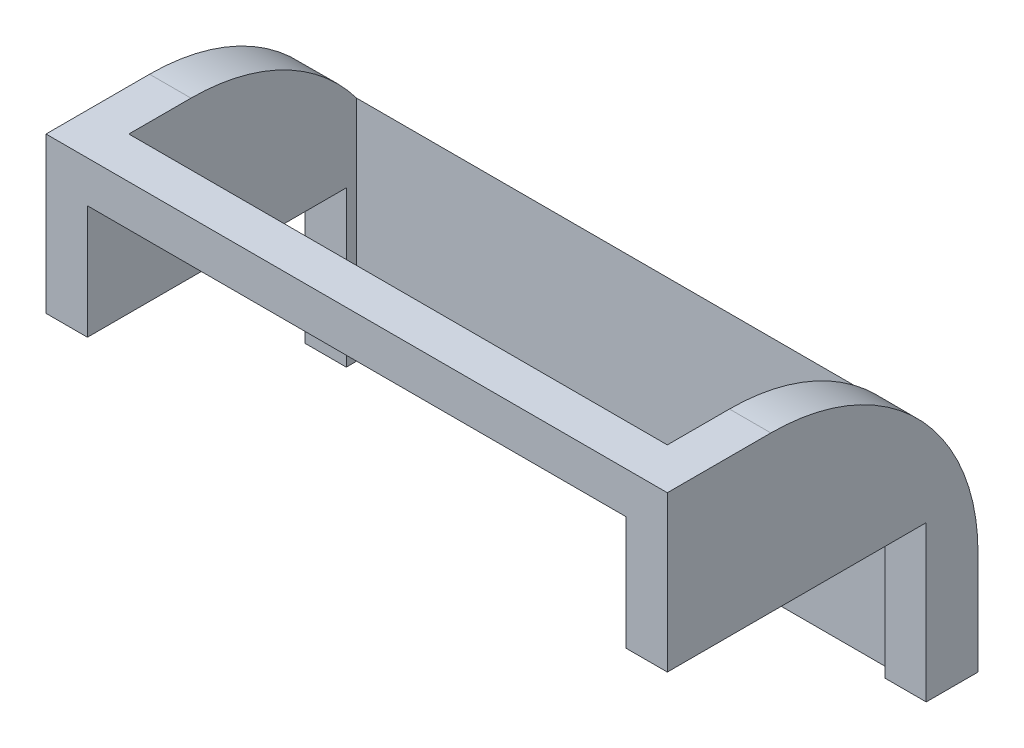
SolidWorks part; units mm, degrees
ref_plane "Front Plane" through (0, 0, 0) normal (0, 0, 1) x (1, 0, 0)
ref_plane "Top Plane" through (0, 0, 0) normal (0, 1, 0) x (1, 0, 0)
ref_plane "Right Plane" through (0, 0, 0) normal (1, 0, 0) x (0, 0, -1)
sketch "Sketch12" plane through (0, 0, 0) normal (0, 1, 0) x (1, 0, 0)
  line L1 (-15, -7.5) -> (15, -7.5)
  line L2 (-15, -7.5) -> (-15, 7.5)
  line L3 (-15, 7.5) -> (15, 7.5)
  line L4 (15, -7.5) -> (15, 7.5)
  line L5 (-15, -7.5) -> (15, 7.5) construction
  line L6 (-15, 7.5) -> (15, -7.5) construction
  point P0 (0, 0)
  dimension "D1" = 15
  dimension "D2" = 30
extrude "Boss-Extrude4" add sketch "Sketch12" along normal blind 15
fillet "Fillet1" radius 10 1 edges at (0, 15, -7.5)
sketch "Sketch13" plane through (0, 0, 0) normal (0, -1, 0) x (1, 0, 0)
  line L1 (13, -5.5) -> (-13, -5.5)
  line L2 (13, -5.5) -> (13, 5.5)
  line L3 (13, 5.5) -> (-13, 5.5)
  line L4 (-13, -5.5) -> (-13, 5.5)
  line L8 (-15, -7.5) -> (-15, 7.5) construction
  line L9 (15, -7.5) -> (-15, -7.5) construction
  line L11 (15, 7.5) -> (15, -7.5) construction
  dimension "D1" = 2
  dimension "D2" = 2
  dimension "D3" = 11
  dimension "D4" = 2
extrude "Cut-Extrude8" cut sketch "Sketch13" against normal through all both and the other way through all
sketch "Sketch14" plane through (0, 0, 7.5) normal (0, 0, 1) x (1, 0, 0)
  line L0 (-15, 15) -> (15, 15) construction
  line L1 (-13, 2) -> (13, 2)
  line L2 (-13, 2) -> (-13, 13)
  line L3 (-13, 13) -> (13, 13)
  line L4 (13, 2) -> (13, 13)
  line L5 (-15, 15) -> (-15, 0) construction
  line L6 (15, 15) -> (15, 0) construction
  line L7 (-15, 0) -> (15, 0) construction
  dimension "D1" = 2
  dimension "D2" = 2
  dimension "D3" = 2
  dimension "D4" = 2
extrude "Cut-Extrude9" cut sketch "Sketch14" against normal blind 10
sketch "Sketch15" plane through (15, 0, 0) normal (1, 0, 0) x (0, 0, -1)
  line L1 (-7.5, 0) -> (5, 0)
  line L2 (-7.5, 0) -> (-7.5, 7.5)
  line L3 (-7.5, 7.5) -> (5, 7.5)
  line L4 (5, 0) -> (5, 7.5)
  dimension "D1" = 7.5
  dimension "D2" = 12.5
extrude "Cut-Extrude10" cut sketch "Sketch15" against normal through all both and the other way through all
